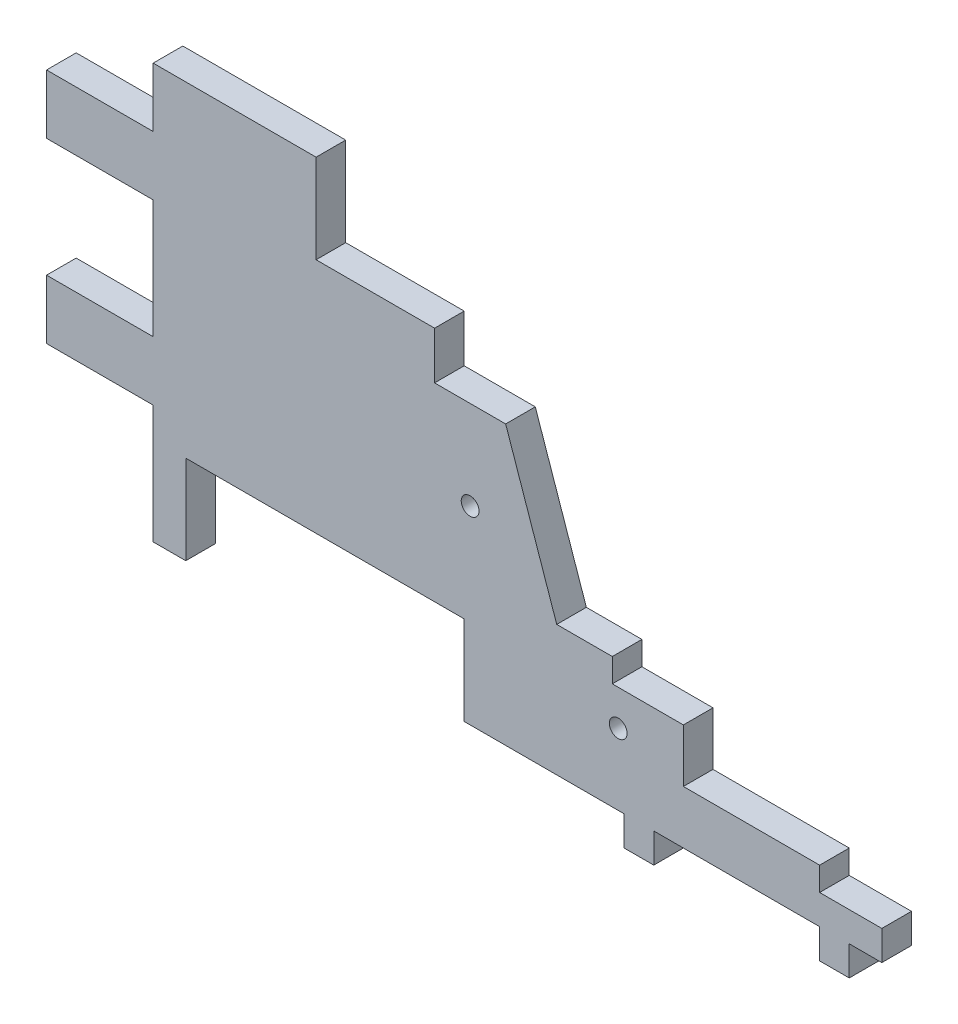
SolidWorks part; units mm, degrees
ref_plane "Plan de face" through (0, 0, 0) normal (0, 0, 1) x (1, 0, 0)
ref_plane "Plan de dessus" through (0, 0, 0) normal (0, 1, 0) x (1, 0, 0)
ref_plane "Plan de droite" through (0, 0, 0) normal (1, 0, 0) x (0, 0, -1)
sketch "Esquisse1" plane through (0, 0, 0) normal (0, 0, 1) x (1, 0, 0)
  line L1 (0, 0) -> (32, 0)
  line L2 (0, 0) -> (0, 47)
  line L3 (0, 47) -> (12, 47)
  line L4 (37, 0) -> (37, 18)
  line L6 (12, 47) -> (22, 18)
  line L7 (22, 18) -> (37, 18)
  line L8 (37, 0) -> (37, -5)
  line L9 (37, -5) -> (32, -5)
  line L10 (32, 0) -> (32, -5)
  circle A0 centre (6, 32) radius 1.5
  circle A1 centre (31, 12) radius 1.5
  dimension "D3" = 20
  dimension "D4" = 3
  dimension "D1" = 6
  dimension "D2" = 12
  dimension "D5" = 15
  dimension "D6" = 6
  dimension "D7" = 25
  dimension "D8" = 10
  dimension "D9" = 6
  dimension "D10" = 5
  dimension "D11" = 5
extrude "Boss.-Extru.1" add sketch "Esquisse1" along normal blind 5
sketch "Esquisse2" plane through (0, 0, 0) normal (0, 0, -1) x (-1, 0, 0)
  line L0 (-37, 18) -> (-22, 18) construction
  line L1 (-37, 0) -> (-65, 0)
  line L2 (-37, 0) -> (-37, 18)
  line L3 (-70, 0) -> (-75.5, 0)
  line L4 (42, 0) -> (47.5, 0)
  line L5 (0, 15) -> (0, 55)
  line L6 (0, 55) -> (20, 55)
  line L7 (47.5, 70) -> (47.5, 60)
  line L8 (0, 0) -> (-32, 0) construction
  line L9 (20, 55) -> (20, 70)
  line L10 (47.5, 50) -> (47.5, 30)
  line L11 (47.5, 20) -> (65.5, 20)
  line L12 (-37, 18) -> (-42, 18)
  line L13 (47.5, 30) -> (65.5, 30)
  line L14 (65.5, 20) -> (65.5, 30)
  line L15 (-70, 0) -> (-70, -5)
  line L16 (-70, -5) -> (-65, -5)
  line L17 (-65, 0) -> (-65, -5)
  line L18 (0, 15) -> (42, 15)
  line L19 (47.5, 60) -> (65.5, 60)
  line L20 (47.5, 20) -> (47.5, 0)
  line L21 (47.5, 50) -> (65.5, 50)
  line L22 (0, 47) -> (0, 0) construction
  line L23 (65.5, 60) -> (65.5, 50)
  line L24 (-42, 18) -> (-42, 9)
  line L25 (-42, 9) -> (-65, 9)
  line L26 (0, 0) -> (-32, 0) construction
  line L27 (42, 15) -> (42, 0)
  line L28 (-37, 18) -> (-22, 18) construction
  line L29 (-37, -5) -> (-37, 18) construction
  line L30 (-65, 9) -> (-65, 5)
  line L31 (-65, 5) -> (-75.5, 5)
  line L32 (-75.5, 5) -> (-75.5, 0)
  line L33 (-32, -5) -> (-37, -5) construction
  line L36 (-30, 18) -> (-22, 18)
  line L37 (-30, 18) -> (-30, 22)
  line L38 (-30, 22) -> (-20.6207, 22)
  line L39 (-22, 18) -> (-20.6207, 22)
  line L40 (-22, 18) -> (-12, 47) construction
  line L41 (20, 70) -> (47.5, 70)
  circle A0 centre (-31, 12) radius 1.5 construction
  dimension "D1" = 38.5
  dimension "D2" = 20
  dimension "D3" = 28
  dimension "D4" = 47.5
  dimension "D5" = 10
  dimension "D6" = 18
  dimension "D7" = 20
  dimension "D8" = 20
  dimension "D9" = 15
  dimension "D10" = 5
  dimension "D11" = 11
  dimension "D12" = 5
  dimension "D13" = 42
  dimension "D14" = 15
  dimension "D15" = 40
  dimension "D16" = 3
  dimension "D17" = 23
  dimension "D22" = 4
  dimension "D23" = 8
extrude "Boss.-Extru.2" add sketch "Esquisse2" against normal blind 5
sketch "Esquisse4" plane through (0, 0, 0) normal (0, 0, -1) x (-1, 0, 0)
  line L0 (0, 0) -> (-32, 0) construction
  line L1 (0, 15) -> (-5, 15)
  line L2 (0, 15) -> (0, 0)
  line L3 (0, 0) -> (-5, 0)
  line L4 (-5, 15) -> (-5, 0)
  dimension "D1" = 5
extrude "Enlèv. mat.-Extru.1" cut sketch "Esquisse4" against normal blind 10
